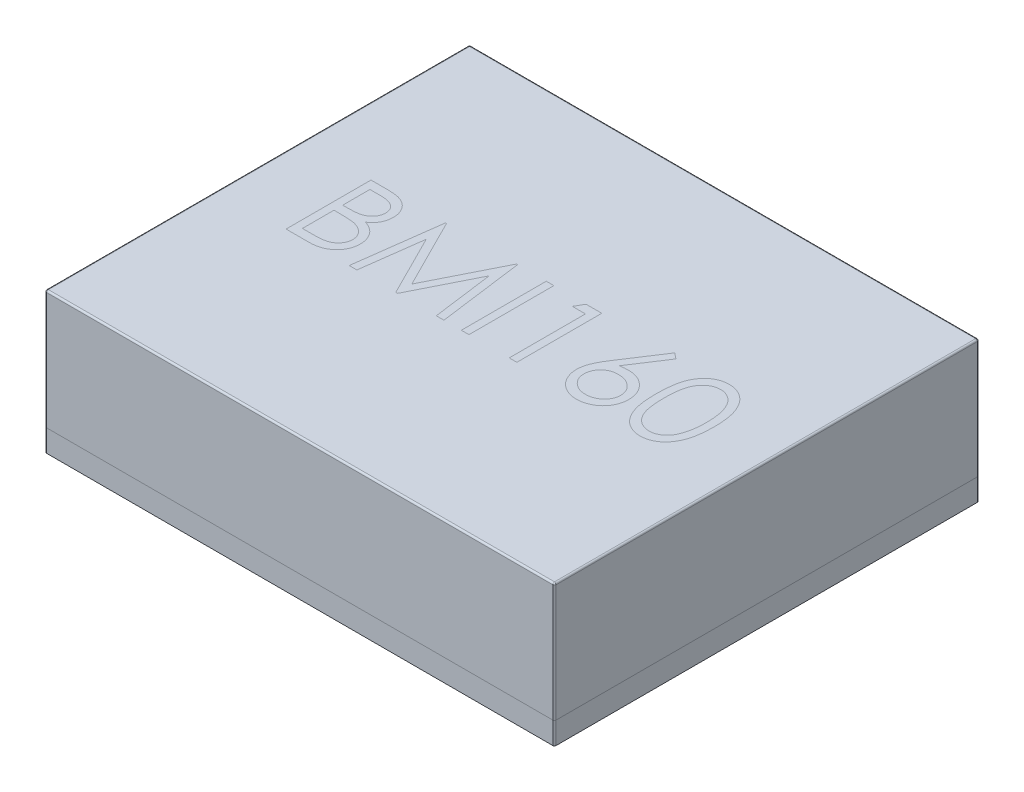
SolidWorks part; units mm, degrees
ref_plane "Ön Düzlem" through (0, 0, 0) normal (0, 0, 1) x (1, 0, 0)
ref_plane "Üst Düzlem" through (0, 0, 0) normal (0, 1, 0) x (1, 0, 0)
ref_plane "Sağ Düzlem" through (0, 0, 0) normal (1, 0, 0) x (0, 0, -1)
sketch "Çizim1" plane through (0, 0, 0) normal (0, 1, 0) x (1, 0, 0)
  line L1 (-1.5, -1.25) -> (1.5, -1.25)
  line L2 (-1.5, -1.25) -> (-1.5, 1.25)
  line L3 (-1.5, 1.25) -> (1.5, 1.25)
  line L4 (1.5, -1.25) -> (1.5, 1.25)
  line L5 (-1.5, -1.25) -> (1.5, 1.25) construction
  line L6 (-1.5, 1.25) -> (1.5, -1.25) construction
  point P0 (0, 0)
  dimension "D1" = 2.5
  dimension "D2" = 3
extrude "Yükseklik-Ekstrüzyon1" add sketch "Çizim1" along normal blind 0.7
sketch "Çizim2" plane through (0, 0, 0) normal (0, -1, 0) x (1, 0, 0)
  line L1 (-1.5, -1.25) -> (1.5, -1.25)
  line L2 (-1.5, -1.25) -> (-1.5, 1.25)
  line L3 (-1.5, 1.25) -> (1.5, 1.25)
  line L4 (1.5, -1.25) -> (1.5, 1.25)
  line L5 (-1.5, -1.25) -> (1.5, 1.25) construction
  line L6 (-1.5, 1.25) -> (1.5, -1.25) construction
  point P0 (0, 0)
extrude "Yükseklik-Ekstrüzyon2" add sketch "Çizim2" along normal blind 0.13 separate body
fillet "Radyus1" radius 0.01 8 edges at (-1.5, 0.35, -1.25) (1.5, 0.35, -1.25) (-1.5, 0.35, 1.25) (1.5, 0.35, 1.25) (0, 0.7, -1.25) (-1.5, 0.7, 0) (1.5, 0.7, 0) (0, 0.7, 1.25)
fillet "Radyus2" radius 0.01 4 edges at (1.5, -0.065, 1.25) (-1.5, -0.065, 1.25) (1.5, -0.065, -1.25) (-1.5, -0.065, -1.25)
sketch "Çizim3" plane through (0, 0.7, 0) normal (0, 1, 0) x (1, 0, 0)
  text T0 "BMI160" font "Century Gothic" height 0.5
extrude "Kes-Ekstrüzyon1" cut sketch "Çizim3" against normal blind 0.1
extrude "Yükseklik-Ekstrüzyon3" add sketch "Çizim3<2>" against normal blind 0.1 separate body
sketch "Çizim3<2>" plane through (0, 0.7, 0) normal (0, 1, 0) x (1, 0, 0) same geometry as "Çizim3"
